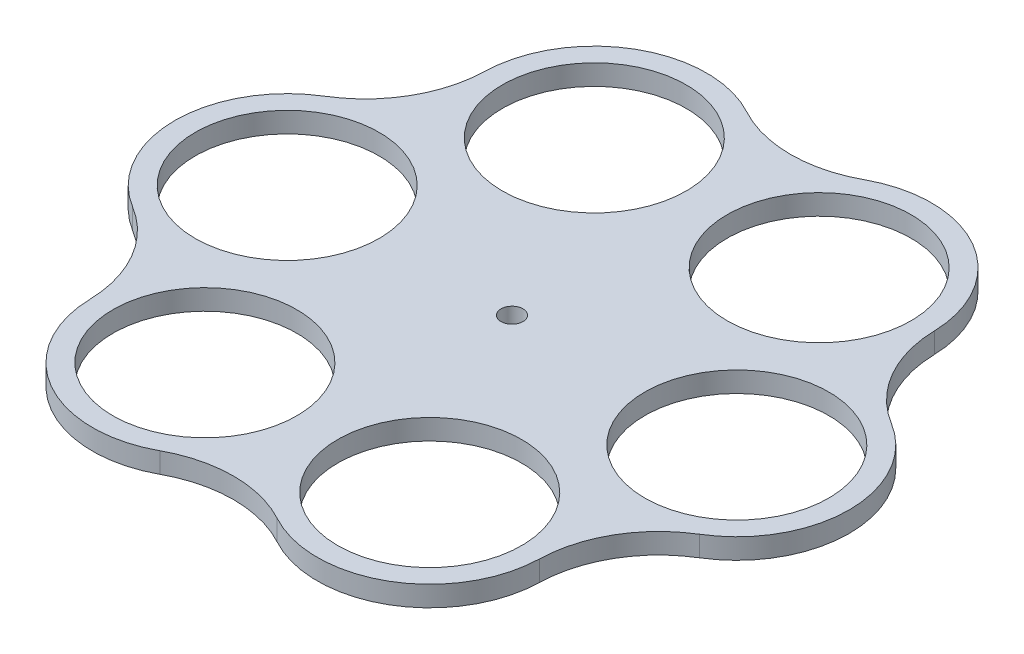
SolidWorks part; units mm, degrees
ref_plane "Front Plane" through (0, 0, 0) normal (0, 0, 1) x (1, 0, 0)
ref_plane "Top Plane" through (0, 0, 0) normal (0, 1, 0) x (1, 0, 0)
ref_plane "Right Plane" through (0, 0, 0) normal (1, 0, 0) x (0, 0, -1)
sketch "Sketch1" plane through (0, 0, 0) normal (0, 1, 0) x (1, 0, 0)
  line L3 (-27.5, 0) -> (-32.5, 0)
  circle A0 centre (27.5, 47.6314) radius 22.5
  circle A1 centre (-27.5, 47.6314) radius 22.5
  circle A2 centre (-55, 0) radius 22.5
  circle A3 centre (-27.5, -47.6314) radius 22.5
  circle A4 centre (27.5, -47.6314) radius 22.5
  circle A5 centre (55, 0) radius 22.5
  arc A6 (54.9915, 48.3168) -> (14.3478, 71.7824) centre (27.5, 47.6314) ccw
  arc A7 (-14.3478, 71.7824) -> (-54.9915, 48.3168) centre (-27.5, 47.6314) ccw
  arc A8 (-69.3393, 23.4656) -> (-69.3393, -23.4656) centre (-55, 0) ccw
  arc A9 (-54.9915, -48.3168) -> (-14.3478, -71.7824) centre (-27.5, -47.6314) ccw
  arc A10 (14.3478, -71.7824) -> (54.9915, -48.3168) centre (27.5, -47.6314) ccw
  arc A11 (69.3393, -23.4656) -> (69.3393, 23.4656) centre (55, 0) ccw
  arc A12 (54.9915, 48.3168) -> (69.3393, 23.4656) centre (84.9821, 49.0645) ccw
  arc A13 (-14.3478, 71.7824) -> (14.3478, 71.7824) centre (0, 98.1289) ccw
  arc A14 (-69.3393, 23.4656) -> (-54.9915, 48.3168) centre (-84.9821, 49.0645) ccw
  arc A15 (-54.9915, -48.3168) -> (-69.3393, -23.4656) centre (-84.9821, -49.0645) ccw
  arc A16 (14.3478, -71.7824) -> (-14.3478, -71.7824) centre (0, -98.1289) ccw
  arc A17 (69.3393, -23.4656) -> (54.9915, -48.3168) centre (84.9821, -49.0645) ccw
  circle A18 centre (0, 0) radius 2.7
extrude "Boss-Extrude1" add sketch "Sketch1" along normal blind 5 contours A17 A11 A12 A6 A13 A7 A14 A8 A15 A9 A16 A10 A18 A5 A4 A3 A1 A0 A2 region at (57.0687, 0, -32.9486)
